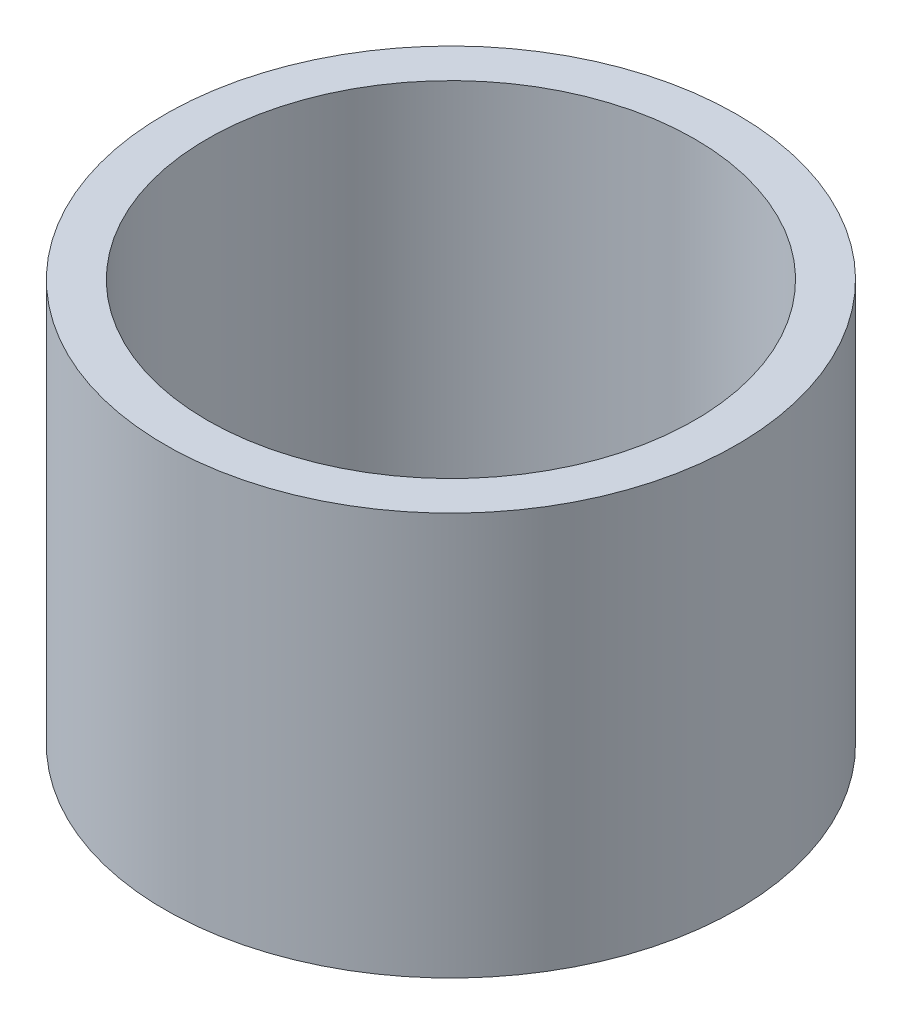
SolidWorks part; units mm, degrees
ref_plane "Front Plane" through (0, 0, 0) normal (0, 0, 1) x (1, 0, 0)
ref_plane "Top Plane" through (0, 0, 0) normal (0, 1, 0) x (1, 0, 0)
ref_plane "Right Plane" through (0, 0, 0) normal (1, 0, 0) x (0, 0, -1)
sketch "Sketch1" plane through (0, 0, 0) normal (0, 1, 0) x (1, 0, 0)
  circle A0 centre (0, 0) radius 1.35
  dimension "D1" = 2.7
extrude "Boss-Extrude1" add sketch "Sketch1" along normal blind 1.9
sketch "Sketch2" plane through (0, 1.9, 0) normal (0, 1, 0) x (1, 0, 0)
  circle A0 centre (0, 0) radius 1.15
  dimension "D1" = 2.3
extrude "Cut-Extrude1" cut sketch "Sketch2" against normal through all
